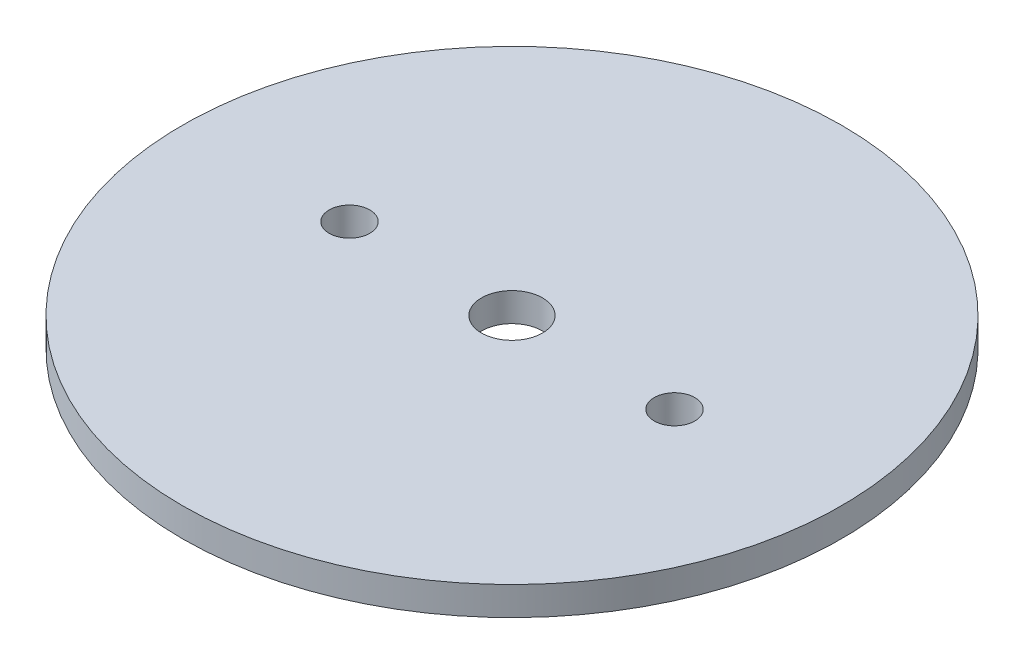
SolidWorks part; units mm, degrees
ref_plane "Front Plane" through (0, 0, 0) normal (0, 0, 1) x (1, 0, 0)
ref_plane "Top Plane" through (0, 0, 0) normal (0, 1, 0) x (1, 0, 0)
ref_plane "Right Plane" through (0, 0, 0) normal (1, 0, 0) x (0, 0, -1)
sketch "Sketch1" plane through (0, 0, 0) normal (0, 1, 0) x (1, 0, 0)
  circle A0 centre (0, 0) radius 36.4998
  dimension "D1" = 72.9996
extrude "Boss-Extrude1" add sketch "Sketch1" along normal mid plane 3.175
hole_wizard "M4 Clearance Hole1" positions "Sketch2" profile "Sketch3" hole size "M4" standard "ANSI Metric" end condition through all
sketch "Sketch2" plane through (0, -1.5875, 0) normal (0, -1, 0) x (-1, 0, 0)
  circle A0 centre (-18, 0) radius 2.85 construction
  circle A1 centre (18, 0) radius 2.85 construction
  point P0 (-18, 0)
  point P2 (18, 0)
  point P5 (0, 0)
  point P8 (0, 0)
sketch "Sketch3" plane through (18, -1.5875, 0) normal (1, 0, 0) x (0, 0, -1)
  line L0 (0, 0) -> (0, 3.175)
  line L1 (0, 3.175) -> (2.25, 3.175)
  line L2 (2.25, 3.175) -> (2.25, 0)
  line L5 (2.25, 0) -> (0, 0)
  line L11 (0, -6.35) -> (0, 107.95) construction
  dimension "Thru Hole Dia." = 4.5
  dimension "Thru Hole Depth" = 3.175
sketch "Sketch4" plane through (0, -1.5875, 0) normal (0, -1, 0) x (1, 0, 0)
  circle A2 centre (0, 0) radius 3.3782
  point P1 (0, 0)
  dimension "D1" = 6.7564
extrude "Cut-Extrude1" cut sketch "Sketch4" against normal through all
